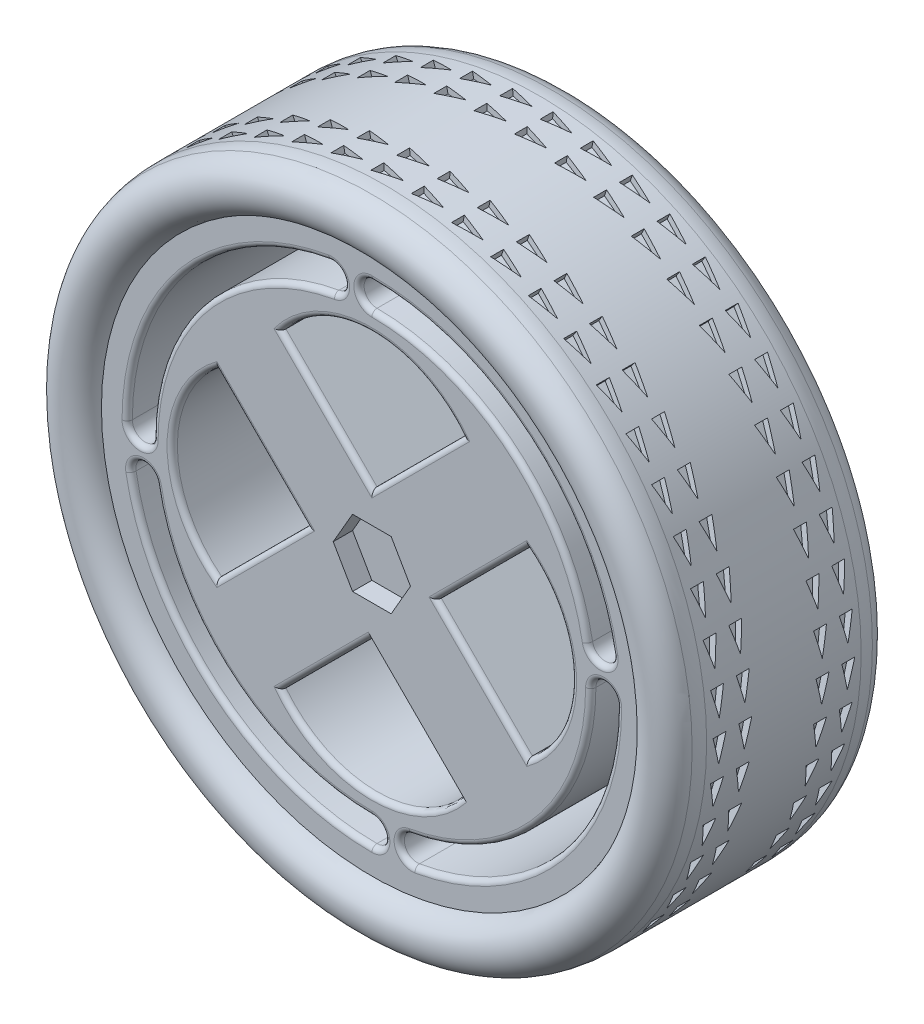
SolidWorks part; units mm, degrees
ref_plane "Ön Düzlem" through (0, 0, 0) normal (0, 0, 1) x (1, 0, 0)
ref_plane "Üst Düzlem" through (0, 0, 0) normal (0, 1, 0) x (1, 0, 0)
ref_plane "Sağ Düzlem" through (0, 0, 0) normal (1, 0, 0) x (0, 0, -1)
sketch "Çizim1" plane through (0, 0, 0) normal (0, 0, 1) x (1, 0, 0)
  circle A0 centre (0, 0) radius 25
  dimension "D1" = 50
extrude "Yükseklik-Ekstrüzyon1" add sketch "Çizim1" along normal mid plane 20
fillet "Radyus3" radius 4 2 edges at (25, 0, 10) (25, 0, -10)
sketch "Çizim3" plane through (0, 0, -10) normal (0, 0, -1) x (-1, 0, 0)
  line L0 (0, 14.1745) -> (0, -14.1745) construction
  circle A0 centre (0, 0) radius 1
  point P4 (0, 0)
  dimension "D1" = 2
extrude "Kes-Ekstrüzyon1" cut sketch "Çizim3" against normal blind 10
sketch "Çizim4" plane through (0, 0, 10) normal (0, 0, 1) x (1, 0, 0)
  line L0 (0, 0) -> (0, 21) construction
  line L1 (0, 5) -> (-5.0987, 5) construction
  line L2 (0, 5) -> (-7.0711, 12.0711)
  line L3 (0, 5) -> (7.0711, 12.0711)
  line L4 (5, 0) -> (12.0711, 7.0711)
  line L5 (5, 0) -> (12.0711, -7.0711)
  line L6 (0, -5) -> (7.0711, -12.0711)
  line L7 (0, -5) -> (-7.0711, -12.0711)
  line L8 (-5, 0) -> (-12.0711, -7.0711)
  line L9 (-5, 0) -> (-12.0711, 7.0711)
  line L10 (-5, 0) -> (-21, 0) construction
  line L11 (0, 5) -> (0, -21) construction
  line L12 (0, 0) -> (21, 0) construction
  circle A0 centre (0, 0) radius 21 construction
  arc A1 (-7.0711, 12.0711) -> (7.0711, 12.0711) centre (0, 6.5033) cw
  arc A2 (12.0711, 7.0711) -> (12.0711, -7.0711) centre (6.5033, 0) cw
  arc A3 (7.0711, -12.0711) -> (-7.0711, -12.0711) centre (0, -6.5033) cw
  arc A4 (-12.0711, -7.0711) -> (-12.0711, 7.0711) centre (-6.5033, 0) cw
  point P26 (0, 0)
  dimension "D2" = 45
  dimension "D5" = 9
  dimension "D7" = 5
  dimension "D1" = 5
  dimension "D3" = 45
  dimension "D4" = 10
  dimension "D6" = 4
extrude "Kes-Ekstrüzyon2" cut sketch "Çizim4" against normal through all
sketch "Çizim5" plane through (0, 0, 10) normal (0, 0, 1) x (1, 0, 0)
  circle A0 centre (0, 0) radius 21 construction
  circle A1 centre (0, 0) radius 21
extrude "Kes-Ekstrüzyon3" cut sketch "Çizim5" against normal blind 3
mirror "Aynalama1" about plane through (0, 0, 0) normal (0, 0, 1) of "Kes-Ekstrüzyon3"
fillet "Radyus5" radius 2 1 edges at (21, 0, 10)
fillet "Radyus6" radius 2 1 edges at (21, 0, -10)
sketch "Çizim6" plane through (0, 0, -7) normal (0, 0, -1) x (-1, 0, 0)
  line L0 (0, 0) -> (0, -21) construction
  line L1 (-21, 0) -> (21, 0) construction
  line L2 (0, 0) -> (21, 0) construction
  circle A0 centre (0, 0) radius 21 construction
  arc A1 (0, 17.9994) -> (-17.7259, 3.1256) centre (0, 0) ccw construction
  arc A14 (0, 18.9994) -> (-18.7108, 3.2992) centre (0, 0) ccw
  arc A19 (0, 16.9994) -> (-16.7411, 2.9519) centre (0, 0) ccw
  arc A20 (0, 16.9994) -> (0, 18.9994) centre (0, 17.9994) ccw
  arc A21 (-18.7108, 3.2992) -> (-16.7411, 2.9519) centre (-17.7259, 3.1256) ccw
  arc A22 (17.9994, 0) -> (3.1256, 17.7259) centre (0, 0) ccw construction
  arc A23 (18.9994, 0) -> (3.2992, 18.7108) centre (0, 0) ccw
  arc A24 (16.9994, 0) -> (2.9519, 16.7411) centre (0, 0) ccw
  arc A25 (16.9994, 0) -> (18.9994, 0) centre (17.9994, 0) ccw
  arc A26 (3.2992, 18.7108) -> (2.9519, 16.7411) centre (3.1256, 17.7259) ccw
  arc A27 (0, -17.9994) -> (17.7259, -3.1256) centre (0, 0) ccw construction
  arc A28 (0, -18.9994) -> (18.7108, -3.2992) centre (0, 0) ccw
  arc A29 (0, -16.9994) -> (16.7411, -2.9519) centre (0, 0) ccw
  arc A30 (0, -16.9994) -> (0, -18.9994) centre (0, -17.9994) ccw
  arc A31 (18.7108, -3.2992) -> (16.7411, -2.9519) centre (17.7259, -3.1256) ccw
  arc A32 (-17.9994, 0) -> (-3.1256, -17.7259) centre (0, 0) ccw construction
  arc A33 (-18.9994, 0) -> (-3.2992, -18.7108) centre (0, 0) ccw
  arc A34 (-16.9994, 0) -> (-2.9519, -16.7411) centre (0, 0) ccw
  arc A35 (-16.9994, 0) -> (-18.9994, 0) centre (-17.9994, 0) ccw
  arc A36 (-3.2992, -18.7108) -> (-2.9519, -16.7411) centre (-3.1256, -17.7259) ccw
  point P7 (-11.5698, 13.7883)
  point P16 (0, 0)
  point P20 (13.7883, 11.5698)
  point P29 (11.5698, -13.7883)
  point P36 (-13.7883, -11.5698)
  point P41 (0, 0)
  dimension "D1" = 23.1396
  dimension "D2" = 17.9994
  dimension "D3" = 2
  dimension "D4" = 4
extrude "Kes-Ekstrüzyon6" cut sketch "Çizim6" against normal through all
fillet "Radyus7" radius 0.4 16 edges at (-17.9994, -1, -7) (-13.0223, 10.927, -7) (-2.1408, 17.8996, -7) (-17.8996, -2.1408, -7) (-12.2126, -14.5544, -7) (1, -17.9994, -7) (2.1408, -17.8996, -7) (14.5544, -12.2126, -7) (17.9994, 1, -7) (17.8996, 2.1408, -7) (12.2126, 14.5544, -7) (-1, 17.9994, -7) (-14.5544, 12.2126, -7) (-10.927, -13.0223, -7) (13.0223, -10.927, -7) (10.927, 13.0223, -7)
fillet "Radyus8" radius 0.4 12 edges at (0, -15.5033, -7) (3.5355, -8.5355, -7) (-3.5355, -8.5355, -7) (-8.5355, -3.5355, -7) (-15.5033, 0, -7) (-8.5355, 3.5355, -7) (-3.5355, 8.5355, -7) (3.5355, 8.5355, -7) (0, 15.5033, -7) (8.5355, -3.5355, -7) (15.5033, 0, -7) (8.5355, 3.5355, -7)
fillet "Radyus9" radius 0.4 27 edges at (-17.8996, -2.1408, 7) (-10.927, -13.0223, 7) (1, -17.9994, 7) (2.1408, -17.8996, 7) (13.0223, -10.927, 7) (17.9994, 1, 7) (17.8996, 2.1408, 7) (10.927, 13.0223, 7) (-1, 17.9994, 7) (-2.1408, 17.8996, 7) (-13.0223, 10.927, 7) (-17.9994, -1, 7) (0, -15.5033, 7) (3.5355, 8.5355, 7) (-3.5355, 8.5355, 7) (-8.5355, 3.5355, 7) (-15.5033, 0, 7) (8.5355, -3.5355, 7) (8.5355, 3.5355, 7) (0, 15.5033, 7) (15.5033, 0, 7) (-3.5355, -8.5355, 7) (-8.5355, -3.5355, 7) (-12.2126, -14.5544, 7) (14.5544, -12.2126, 7) (12.2126, 14.5544, 7) (-14.5544, 12.2126, 7)
sketch "Çizim7" plane through (0, 0, 7) normal (0, 0, 1) x (1, 0, 0)
  line L0 (9.8995, -9.8995) -> (-9.8995, 9.8995) construction
  line L3 (-12.0346, 7.6003) -> (-4.4343, 0) construction
  line L6 (3, 0) -> (1.5, 2.5981)
  line L7 (1.5, 2.5981) -> (-1.5, 2.5981)
  line L8 (-1.5, 2.5981) -> (-3, 0)
  line L9 (-3, 0) -> (-1.5, -2.5981)
  line L10 (-1.5, -2.5981) -> (1.5, -2.5981)
  line L11 (1.5, -2.5981) -> (3, 0)
  circle A0 centre (0, 0) radius 2.5981 construction
  point P3 (0, 0)
  dimension "D1" = 14
  dimension "D2" = 6
extrude "Kes-Ekstrüzyon7" cut sketch "Çizim7" against normal blind 1.5
ref_plane "Düzlem1" through (-25, 0, 0) normal (1, 0, 0) x (0, 0, -1)
sketch "Çizim8" plane through (-25, 0, 0) normal (1, 0, 0) x (0, 0, -1)
  line L0 (-6, 0) -> (6, 0) construction
  line L1 (6, 25) -> (6, -25) construction
  line L2 (3.5, 0) -> (3.0045, 2)
  line L3 (3.0045, 2) -> (2.5, 0)
  line L4 (2.5, 0) -> (3.5, 0)
  line L5 (0, 0) -> (0, 3.0449) construction
  line L6 (4, 0) -> (4, 2.7898) construction
  line L7 (5.5, 0) -> (4.5, 0)
  line L8 (4.9955, 2) -> (5.5, 0)
  line L9 (4.5, 0) -> (4.9955, 2)
  line L10 (-4.9955, 2) -> (-5.5, 0)
  line L11 (-5.5, 0) -> (-4.5, 0)
  line L12 (-4.5, 0) -> (-4.9955, 2)
  line L13 (-2.5, 0) -> (-3.5, 0)
  line L14 (-3.5, 0) -> (-3.0045, 2)
  line L15 (-3.0045, 2) -> (-2.5, 0)
  point P6 (0, 0)
  dimension "D1" = 2.5
  dimension "D2" = 2
  dimension "D3" = 3.5
  dimension "D4" = 3.0045
  dimension "D5" = 0.5
extrude "Kes-Ekstrüzyon8" cut sketch "Çizim8" along normal blind 0.5
pattern_circular "Dairesel Kaplama1" count 50 over 360 about axis through (0, 0, 10) along (0, 0, -1) of "Kes-Ekstrüzyon8" reverse direction yes
